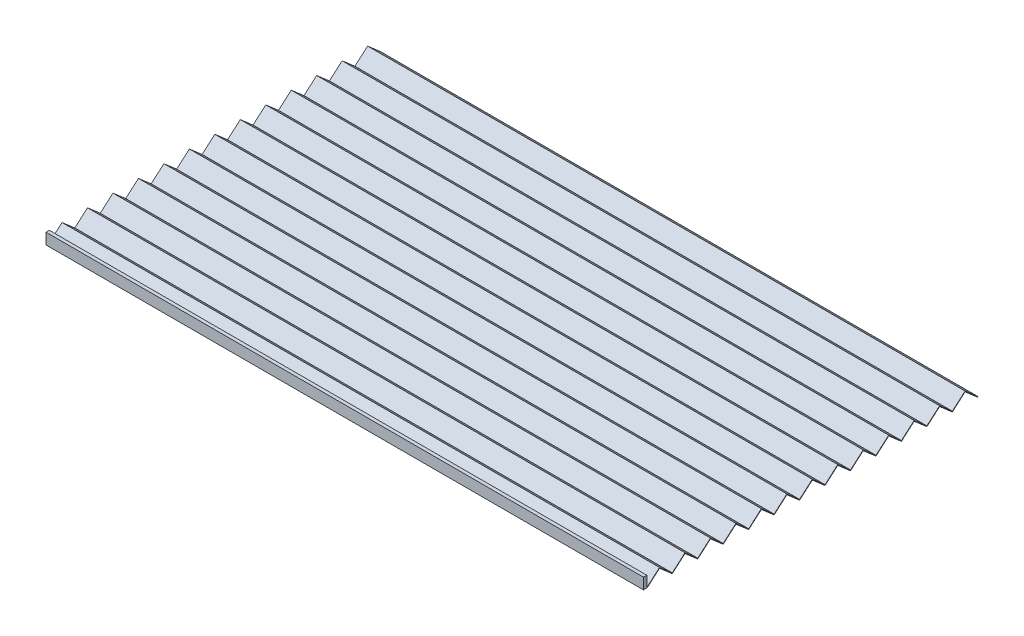
SolidWorks part; units mm, degrees
ref_plane "Front Plane" through (0, 0, 0) normal (0, 0, 1) x (1, 0, 0)
ref_plane "Top Plane" through (0, 0, 0) normal (0, 1, 0) x (1, 0, 0)
ref_plane "Right Plane" through (0, 0, 0) normal (1, 0, 0) x (0, 0, -1)
sketch "Sketch2" plane through (0, 0, 0) normal (0, 0, 1) x (1, 0, 0)
  line L1 (-270, 10) -> (270, 10)
  line L2 (-270, 10) -> (-270, 0)
  line L3 (-270, 0) -> (270, 0)
  line L4 (270, 10) -> (270, 0)
  point P4 (0, 0)
  dimension "D1" = 10
  dimension "D2" = 540
extrude "Boss-Extrude1" add sketch "Sketch2" along normal blind 3
sketch "Sketch3" plane through (270, 0, 0) normal (1, 0, 0) x (0, 0, -1)
  line L0 (0, 10) -> (299.1683, 10) construction
  line L1 (0, 0) -> (299.1683, 0) construction
  line L3 (0, 0) -> (11.5065, 10)
  line L4 (11.5065, 10) -> (23.0129, 0)
  line L5 (23.0129, 0) -> (34.5194, 10)
  line L6 (34.5194, 10) -> (46.0259, 0)
  line L7 (46.0259, 0) -> (57.5324, 10)
  line L8 (57.5324, 10) -> (69.0388, 0)
  line L9 (69.0388, 0) -> (80.5453, 10)
  line L10 (80.5453, 10) -> (92.0518, 0)
  line L11 (92.0518, 0) -> (103.5583, 10)
  line L12 (103.5583, 10) -> (115.0647, 0)
  line L13 (115.0647, 0) -> (126.5712, 10)
  line L14 (126.5712, 10) -> (138.0777, 0)
  line L15 (138.0777, 0) -> (149.5842, 10)
  line L16 (149.5842, 10) -> (161.0906, 0)
  line L17 (161.0906, 0) -> (172.5971, 10)
  line L18 (172.5971, 10) -> (184.1036, 0)
  line L20 (184.1036, 0) -> (195.6101, 10)
  line L21 (195.6101, 10) -> (207.1165, 0)
  line L22 (207.1165, 0) -> (218.623, 10)
  line L23 (218.623, 10) -> (230.1295, 0)
  line L24 (230.1295, 0) -> (241.636, 10)
  line L25 (241.636, 10) -> (253.1424, 0)
  line L26 (253.1424, 0) -> (264.6489, 10)
  line L27 (264.6489, 10) -> (276.1554, 0)
  line L28 (276.1554, 0) -> (287.6619, 10)
  line L29 (287.6619, 10) -> (299.1683, 0)
  line L30 (299.1683, 10) -> (299.1683, 0) construction
  line L32 (299.1683, 10) -> (299.1683, 0) construction
extrude "Extrude-Thin1" add sketch "Sketch3" against normal through all thin thin type mid plane wall 0.5
